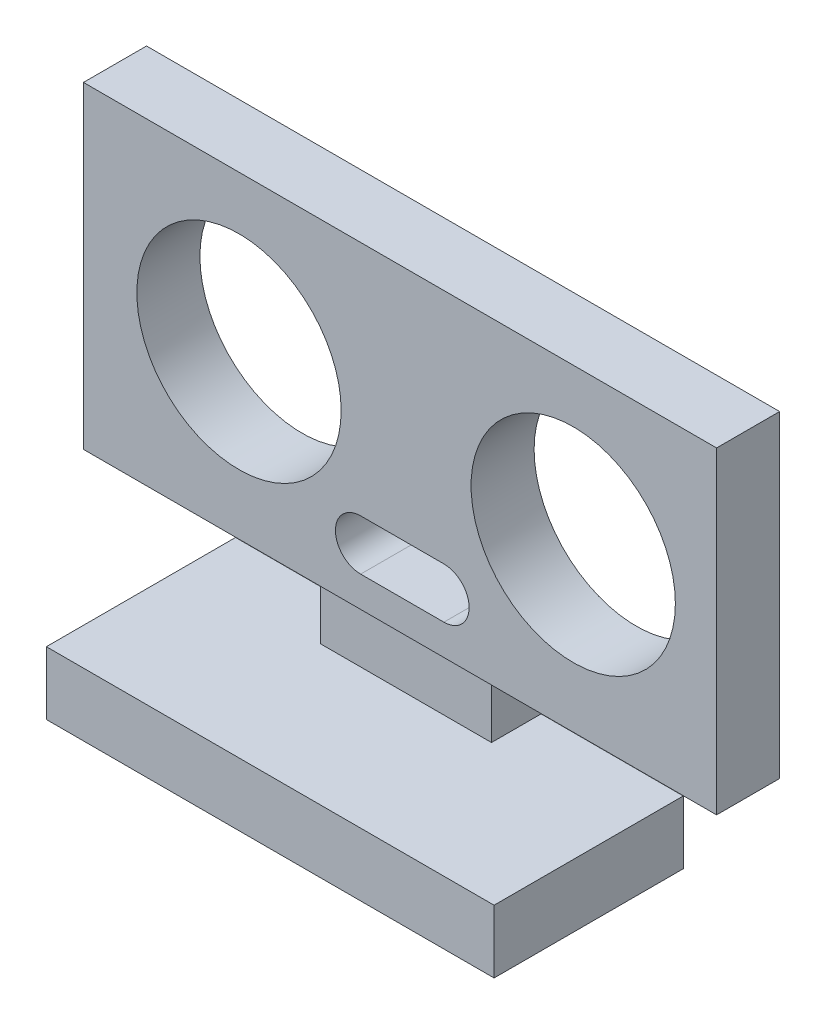
SolidWorks part; units mm, degrees
ref_plane "Front Plane" through (0, 0, 0) normal (0, 0, 1) x (1, 0, 0)
ref_plane "Top Plane" through (0, 0, 0) normal (0, 1, 0) x (1, 0, 0)
ref_plane "Right Plane" through (0, 0, 0) normal (1, 0, 0) x (0, 0, -1)
sketch "Sketch1" plane through (0, 0, 0) normal (0, 1, 0) x (1, 0, 0)
  line L0 (14.5041, 9.9599) -> (50.0041, 9.9599)
  line L5 (14.5041, 21.2754) -> (50.0041, 21.2754)
  line L10 (14.5041, 21.2754) -> (14.5041, 6.2754)
  line L11 (14.5041, 6.2754) -> (50.0041, 6.2754)
  line L12 (50.0041, 21.2754) -> (50.0041, 6.2754)
  line L13 (14.5041, 14.0701) -> (50.0041, 14.1179)
  dimension "D1" = 35.5
  dimension "D2" = 15
extrude "Boss-Extrude7" add sketch "Sketch1" along normal blind 5 contours L13 L12 L5 L10 | L13 L10 L0 L12 | L0 L10 L11 L12 region at (32.2883, 0, -12.0269) region at (32.2541, 0, -8.1176) region at (32.2344, 0, -17.6847)
sketch "Sketch5" plane through (0, 5, 0) normal (0, 1, 0) x (1, 0, 0)
  line L0 (14.5041, 21.2754) -> (50.0041, 21.2754) construction
  line L1 (25.1665, 21.2754) -> (38.7336, 21.2754)
  line L2 (25.1665, 21.2754) -> (25.1665, 17.3426)
  line L3 (25.1665, 17.3426) -> (38.7336, 17.3426)
  line L4 (38.7336, 21.2754) -> (38.7336, 17.3426)
extrude "Boss-Extrude8" add sketch "Sketch5" along normal blind 5
sketch "Sketch6" plane through (1.1246, 10, 0) normal (0, 1, 0) x (1, 0, 0)
  line L2 (6.3022, 21.2948) -> (56.5022, 21.2948)
  line L3 (6.3022, 21.2948) -> (6.3022, 16.2948)
  line L4 (6.3022, 16.2948) -> (56.5022, 16.2948)
  line L5 (56.5022, 21.2948) -> (56.5022, 16.2948)
  dimension "D1" = 50.2
  dimension "D2" = 5
extrude "Boss-Extrude9" add sketch "Sketch6" along normal blind 25.2 contours L3 L2 L5 L4
sketch "Sketch7" plane through (0, 0, -16.2948) normal (0, 0, 1) x (1, 0, 0)
  line L0 (19.7589, 22.8759) -> (46.2589, 22.8759)
  line L2 (29.4061, 14.4257) -> (36.0061, 14.4257) construction
  line L3 (29.4061, 16.4257) -> (36.0061, 16.4257)
  line L4 (29.4061, 12.4257) -> (36.0061, 12.4257)
  circle A0 centre (19.7589, 22.8759) radius 8.1
  circle A1 centre (46.2589, 22.8759) radius 8.1
  arc A2 (29.4061, 16.4257) -> (29.4061, 12.4257) centre (29.4061, 14.4257) ccw
  arc A3 (36.0061, 12.4257) -> (36.0061, 16.4257) centre (36.0061, 14.4257) ccw
  point P8 (32.7061, 14.4257)
  dimension "D1" = 16.2
  dimension "D4" = 2
  dimension "D2" = 26.5
  dimension "D3" = 6.6
extrude "Cut-Extrude1" cut sketch "Sketch7" against normal blind 10 contours A0 | A1 region at (46.2589, 30.7468, -16.2948) region at (11.888, 22.8759, -16.2948)
extrude "Cut-Extrude2" cut sketch "Sketch7<3>" against normal blind 10 contours L4 A3 L3 A2 region at (32.7061, 14.4257, -16.2948)
sketch "Sketch7<3>" plane through (0, 0, -16.2948) normal (0, 0, 1) x (1, 0, 0) same geometry as "Sketch7"
